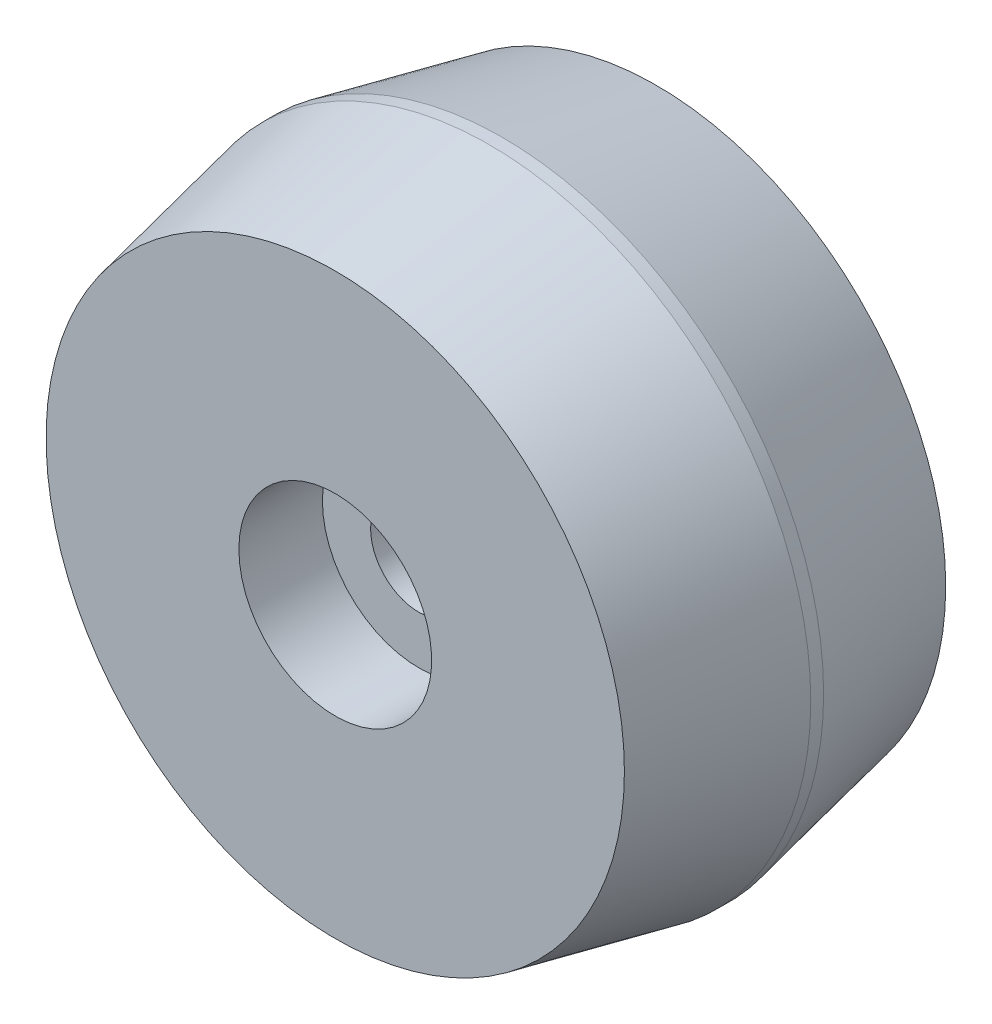
SolidWorks part; units mm, degrees
ref_plane "前视基准面" through (0, 0, 0) normal (0, 0, 1) x (1, 0, 0)
ref_plane "上视基准面" through (0, 0, 0) normal (0, 1, 0) x (1, 0, 0)
ref_plane "右视基准面" through (0, 0, 0) normal (1, 0, 0) x (0, 0, -1)
other "Configuration Table"
sketch "草图1" plane through (0, 0, 0) normal (0, 0, 1) x (1, 0, 0)
  circle A0 centre (0, 0) radius 10
  dimension "D1" = 20
extrude "凸台-拉伸1" add sketch "草图1" along normal blind 10
chamfer "倒角1" distance 1 distance2 4.8 1 edges at (10, 0, 0) first distance on face at (10, 0, 0)
chamfer "倒角2" distance 4.8 distance2 1 1 edges at (10, 0, 10) first distance on face at (10, 0, 4.8)
sketch "草图2" plane through (0, 0, 0) normal (0, 0, -1) x (-1, 0, 0)
  circle A0 centre (0, 0) radius 3
  dimension "D1" = 6
extrude "切除-拉伸1" cut sketch "草图2" against normal blind 2.6
extrude "切除-拉伸2" cut sketch "草图2<3>" along normal blind 2.6 from offset 10 offset against normal yes
sketch "草图2<3>" plane through (0, 0, 0) normal (0, 0, -1) x (-1, 0, 0) same geometry as "草图2"
sketch "草图4" plane through (0, 0, 2.6) normal (0, 0, -1) x (-1, 0, 0)
  circle A0 centre (0, 0) radius 1.5
  dimension "D1" = 3
extrude "切除-拉伸3" cut sketch "草图4" against normal through all
